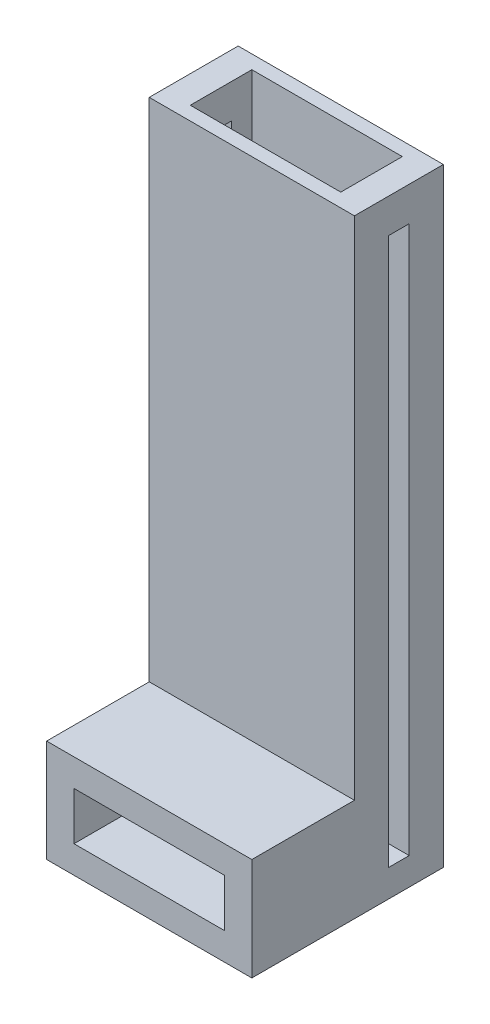
SolidWorks part; units mm, degrees
ref_plane "Front Plane" through (0, 0, 0) normal (0, 0, 1) x (1, 0, 0)
ref_plane "Top Plane" through (0, 0, 0) normal (0, 1, 0) x (1, 0, 0)
ref_plane "Right Plane" through (0, 0, 0) normal (1, 0, 0) x (0, 0, -1)
sketch "Sketch1" plane through (0, 0, 0) normal (0, 1, 0) x (1, 0, 0)
  line L1 (0, 0) -> (30, 0)
  line L2 (0, 0) -> (0, -13)
  line L3 (0, -13) -> (30, -13)
  line L4 (30, 0) -> (30, -13)
  dimension "D1" = 30
  dimension "D2" = 13
extrude "Boss-Extrude1" add sketch "Sketch1" along normal blind 85
sketch "Sketch2" plane through (0, 85, 0) normal (0, 1, 0) x (1, 0, 0)
  line L0 (0, -6.5) -> (30, -6.5) construction
  line L1 (0, 0) -> (0, -13) construction
  line L2 (30, -13) -> (30, 0) construction
  line L4 (4, -11) -> (26, -11)
  line L5 (4, -11) -> (4, -2)
  line L6 (4, -2) -> (26, -2)
  line L7 (26, -11) -> (26, -2)
  line L8 (4, -11) -> (26, -2) construction
  line L9 (4, -2) -> (26, -11) construction
  point P6 (15, -6.5)
  dimension "D1" = 22
  dimension "D2" = 9
extrude "Cut-Extrude2" cut sketch "Sketch2" against normal blind 85
sketch "Sketch5" plane through (0, 0, 0) normal (0, 1, 0) x (1, 0, 0)
  line L1 (0, 0) -> (30, 0)
  line L2 (0, 0) -> (0, -13)
  line L3 (0, -13) -> (30, -13)
  line L4 (30, 0) -> (30, -13)
extrude "Boss-Extrude3" add sketch "Sketch5" against normal blind 4
sketch "Sketch7" plane through (0, 85, 0) normal (0, 1, 0) x (1, 0, 0)
  line L0 (4, -13) -> (4, 0) construction
  line L1 (0, -13) -> (30, -13) construction
  line L2 (30, 0) -> (0, 0) construction
  line L3 (26, -13) -> (26, 0) construction
sketch "Sketch10" plane through (0, 85, 0) normal (0, 1, 0) x (1, 0, 0)
  line L0 (4, -13) -> (0, -13) construction
sketch "Sketch12" plane through (0, 0, 13) normal (0, 0, 1) x (1, 0, 0)
  line L0 (0, -4) -> (0, 0) construction
  line L1 (0, 85) -> (0, -4) construction
  line L2 (0, -4) -> (4, -4) construction
  line L3 (0, -4) -> (30, -4) construction
  line L4 (4, -4) -> (4, 0) construction
  line L5 (4, 0) -> (4, 7) construction
  line L7 (4, 0) -> (26, 0)
  line L8 (4, 0) -> (4, 7)
  line L9 (4, 7) -> (26, 7)
  line L10 (26, 0) -> (26, 7)
  dimension "D1" = 22
extrude "Cut-Extrude4" cut sketch "Sketch12" against normal blind 13 contours L9 L10 L7 L8
sketch "Sketch13" plane through (0, 0, 0) normal (-1, 0, 0) x (0, 0, 1)
  line L0 (0, -4) -> (13, -4) construction
  line L1 (5, -4) -> (8, -4) construction
  line L2 (6.5, -4) -> (6.5, 0) construction
  line L3 (6.5, 0) -> (5, 0) construction
  line L5 (5, 0) -> (8, 0)
  line L6 (5, 0) -> (5, 80)
  line L7 (5, 80) -> (8, 80)
  line L8 (8, 0) -> (8, 80)
  point P7 (6.5, -4)
  dimension "D1" = 3
  dimension "D2" = 80
extrude "Cut-Extrude5" cut sketch "Sketch13" against normal through all
sketch "Sketch14" plane through (0, 0, 13) normal (0, 0, 1) x (1, 0, 0)
  line L0 (30, 85) -> (30, -4) construction
  line L1 (4, 7) -> (26, 7) construction
  line L2 (4, 7) -> (4, 0) construction
  line L3 (4, 0) -> (26, 0) construction
  line L4 (26, 7) -> (26, 0) construction
  line L5 (0, -4) -> (30, -4)
  line L6 (0, -4) -> (0, 11)
  line L7 (0, 11) -> (30, 11)
  line L8 (30, -4) -> (30, 11)
  line L9 (26, 3.5) -> (30, 3.5) construction
  line L10 (15, 7) -> (15, 11) construction
extrude "Boss-Extrude4" add sketch "Sketch14" along normal blind 15
sketch "Sketch15" plane through (0, 0, 28) normal (0, 0, 1) x (1, 0, 0)
  line L0 (0, 3.5) -> (4, 3.5) construction
  line L1 (0, 11) -> (0, -4) construction
  line L2 (15, -4) -> (15, 0) construction
  line L3 (0, -4) -> (30, -4) construction
  line L4 (30, 3.5) -> (26, 3.5) construction
  line L5 (30, -4) -> (30, 11) construction
  line L6 (15, 11) -> (15, 7) construction
  line L7 (30, 11) -> (0, 11) construction
  line L8 (4, 0) -> (26, 0)
  line L9 (26, 0) -> (26, 7)
  line L10 (26, 7) -> (4, 7)
  line L11 (4, 7) -> (4, 0)
extrude "Cut-Extrude6" cut sketch "Sketch15" against normal blind 15
